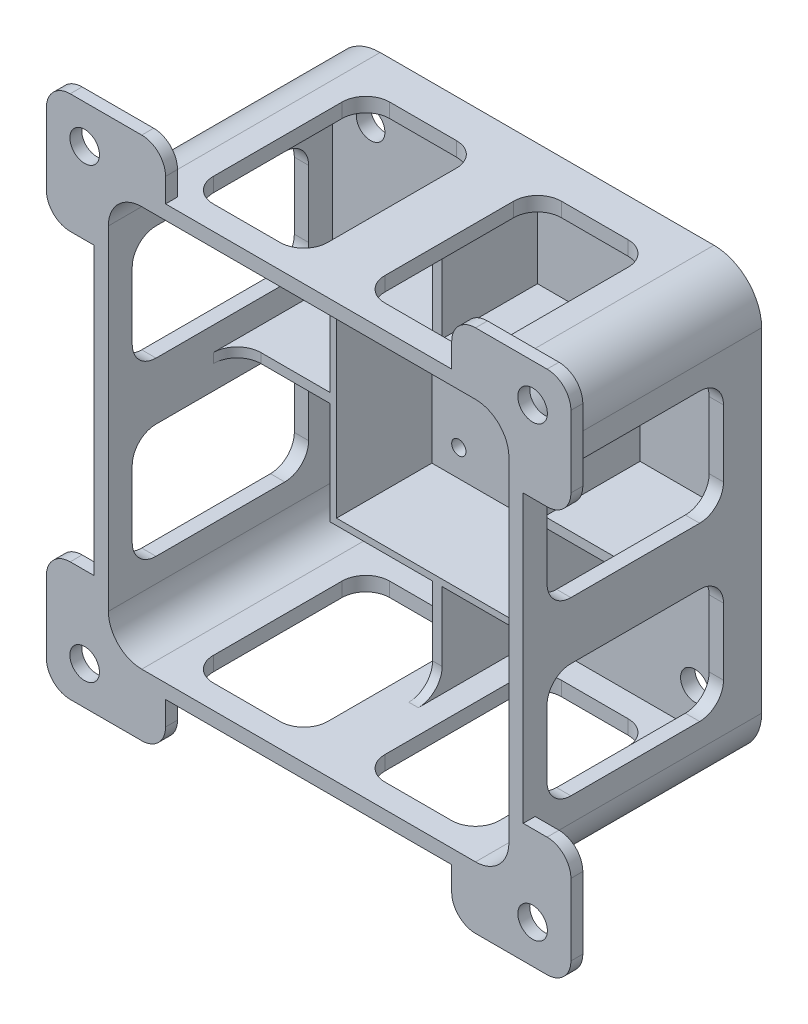
SolidWorks part; units mm, degrees
material "尼龙 101"
ref_plane "前视基准面" through (0, 0, 0) normal (0, 0, 1) x (1, 0, 0)
ref_plane "上视基准面" through (0, 0, 0) normal (0, 1, 0) x (1, 0, 0)
ref_plane "右视基准面" through (0, 0, 0) normal (1, 0, 0) x (0, 0, -1)
sketch "草图1" plane through (0, 0, 0) normal (0, 0, 1) x (1, 0, 0)
  line L1 (-35, 45) -> (35, 45)
  line L2 (-45, 35) -> (-45, -35)
  line L3 (-35, -45) -> (35, -45)
  line L4 (45, 35) -> (45, -35)
  line L5 (-45, 45) -> (45, -45) construction
  line L6 (-45, -45) -> (45, 45) construction
  arc A0 (-45, -35) -> (-35, -45) centre (-35, -35) ccw
  arc A1 (35, -45) -> (45, -35) centre (35, -35) ccw
  arc A2 (35, 45) -> (45, 35) centre (35, 35) cw
  arc A3 (-35, 45) -> (-45, 35) centre (-35, 35) ccw
  point P0 (0, 0)
  dimension "D3" = 10
  dimension "D1" = 90
  dimension "D2" = 90
extrude "凸台-拉伸1" add sketch "草图1" along normal blind 50
shell "抽壳1" thickness 3 removed face at (0, 0, 50)
sketch "草图3" plane through (0, 0, 50) normal (0, 0, 1) x (1, 0, 0)
  line L1 (0, 0) -> (0, 55.6478) construction
  line L2 (0, 0) -> (103.6974, 0) construction
  circle A0 centre (-34, 34) radius 3
  circle A1 centre (34, 34) radius 3
  circle A2 centre (34, -34) radius 3
  circle A3 centre (-34, -34) radius 3
  dimension "D3" = 6
  dimension "D4" = 6
  dimension "D5" = 6
  dimension "D6" = 6
  dimension "D1" = 68
  dimension "D2" = 68
extrude "切除-拉伸1" cut sketch "草图3" against normal up to next
sketch "草图4" plane through (0, 0, 3) normal (0, 0, 1) x (1, 0, 0)
  line L1 (-21.15, -21.15) -> (21.15, -21.15)
  line L2 (-21.15, -21.15) -> (-21.15, 21.15)
  line L3 (-21.15, 21.15) -> (21.15, 21.15)
  line L4 (21.15, -21.15) -> (21.15, 21.15)
  line L5 (-21.15, -21.15) -> (21.15, 21.15) construction
  line L6 (-21.15, 21.15) -> (21.15, -21.15) construction
  line L7 (-22.5, -22.5) -> (22.5, -22.5)
  line L8 (-22.5, -22.5) -> (-22.5, 22.5)
  line L9 (-22.5, 22.5) -> (22.5, 22.5)
  line L10 (22.5, -22.5) -> (22.5, 22.5)
  line L11 (-22.5, -22.5) -> (22.5, 22.5) construction
  line L12 (-22.5, 22.5) -> (22.5, -22.5) construction
  point P0 (0, 0)
  point P6 (0, 0)
  dimension "D1" = 42.3
  dimension "D2" = 42.3
  dimension "D3" = 45
  dimension "D4" = 45
extrude "凸台-拉伸3" add sketch "草图4" along normal blind 20
sketch "草图11" plane through (0, 0, 3) normal (0, 0, 1) x (1, 0, 0)
  line L0 (-15.5, -15.5) -> (-15.5, 15.5) construction
  line L1 (-15.5, 15.5) -> (15.5, 15.5) construction
  line L2 (15.5, 15.5) -> (15.5, -15.5) construction
  line L3 (15.5, -15.5) -> (-15.5, -15.5) construction
  line L4 (0, 0) -> (34.4126, 0) construction
  line L5 (0, 0) -> (0, 49.7231) construction
  circle A0 centre (-15.5, -15.5) radius 1.5
  circle A1 centre (15.5, -15.5) radius 1.5
  circle A2 centre (15.5, 15.5) radius 1.5
  circle A3 centre (-15.5, 15.5) radius 1.5
  dimension "D3" = 3
  dimension "D4" = 3
  dimension "D5" = 3
  dimension "D6" = 3
  dimension "D1" = 31
  dimension "D2" = 31
extrude "切除-拉伸4" cut sketch "草图11" against normal through all
sketch "草图7" plane through (0, 0, 3) normal (0, 0, 1) x (1, 0, 0)
  line L0 (22.5, 22.5) -> (-22.5, 22.5) construction
  line L1 (-1, 42) -> (1, 42)
  line L2 (-1, 42) -> (-1, 22.5)
  line L3 (-1, 22.5) -> (1, 22.5)
  line L4 (1, 42) -> (1, 22.5)
  line L5 (-1, 42) -> (1, 22.5) construction
  line L6 (-1, 22.5) -> (1, 42) construction
  line L7 (-35, -42) -> (35, -42) construction
  line L8 (-1, -22.5) -> (1, -22.5)
  line L9 (-1, -22.5) -> (-1, -42)
  line L10 (-1, -42) -> (1, -42)
  line L11 (1, -22.5) -> (1, -42)
  line L12 (-1, -22.5) -> (1, -42) construction
  line L13 (-1, -42) -> (1, -22.5) construction
  line L14 (0, 32.25) -> (0, 0) construction
  line L15 (0, 0) -> (0, -32.25) construction
  line L16 (35, 42) -> (-35, 42) construction
  line L17 (-22.5, -22.5) -> (22.5, -22.5) construction
  point P0 (0, 32.25)
  point P7 (0, -32.25)
  dimension "D1" = 2
  dimension "D2" = 2
extrude "凸台-拉伸5" add sketch "草图7" along normal up to surface (20 mm away) up to face at (0, 0, 23)
ref_axis "基准轴1" through (0, 0, -2) along (0, 0, 1)
pattern_circular "阵列(圆周)1" count 2 over 90 about axis through (0, 0, -2) along (0, 0, 1) of "凸台-拉伸5"
sketch "草图10" plane through (0, 0, 0) normal (0, 0, -1) x (-1, 0, 0)
  circle A0 centre (0, 0) radius 5
  dimension "D1" = 10
extrude "切除-拉伸3" cut sketch "草图10" against normal through all
fillet "圆角1" radius 5 4 edges at (-42, 0, 23) (42, 0, 23) (0, -42, 23) (0, 42, 23)
sketch "草图12" plane through (0, 0, 50) normal (0, 0, 1) x (1, 0, 0)
  line L5 (42, -30) -> (50, -30)
  line L6 (30, -42) -> (30, -50)
  line L7 (35, -55) -> (50, -55)
  line L8 (55, -35) -> (55, -50)
  line L19 (42, -35) -> (42, 35) construction
  line L20 (35, -42) -> (30, -42)
  line L21 (-35, -42) -> (35, -42) construction
  line L22 (42, -35) -> (42, -30)
  line L23 (0, 0) -> (0, -109.4281) construction
  line L24 (-42, -35) -> (-42, -30)
  line L25 (-35, -42) -> (-30, -42)
  line L27 (-55, -35) -> (-55, -50)
  line L28 (-35, -55) -> (-50, -55)
  line L29 (-30, -42) -> (-30, -50)
  line L30 (-42, -30) -> (-50, -30)
  line L36 (45, -35) -> (45, 35) construction
  line L37 (-35, -45) -> (35, -45) construction
  line L38 (0, 0) -> (81.8006, 0) construction
  line L39 (-42, 30) -> (-50, 30)
  line L40 (-30, 42) -> (-30, 50)
  line L41 (-35, 55) -> (-50, 55)
  line L42 (-55, 35) -> (-55, 50)
  line L43 (-35, 42) -> (-30, 42)
  line L44 (-42, 35) -> (-42, 30)
  line L45 (42, 35) -> (42, 30)
  line L46 (35, 42) -> (30, 42)
  line L47 (55, 35) -> (55, 50)
  line L48 (35, 55) -> (50, 55)
  line L49 (30, 42) -> (30, 50)
  line L50 (42, 30) -> (50, 30)
  arc A1 (-42, 35) -> (-35, 42) centre (-35, 35) cw
  arc A2 (-30, 50) -> (-35, 55) centre (-35, 50) ccw
  arc A3 (-50, 55) -> (-55, 50) centre (-50, 50) ccw
  arc A4 (42, -35) -> (35, -42) centre (35, -35) cw
  arc A5 (30, -50) -> (35, -55) centre (35, -50) ccw
  arc A6 (50, -55) -> (55, -50) centre (50, -50) ccw
  arc A7 (50, -30) -> (55, -35) centre (50, -35) cw
  arc A22 (-50, -30) -> (-55, -35) centre (-50, -35) ccw
  arc A23 (-50, -55) -> (-55, -50) centre (-50, -50) cw
  arc A24 (-30, -50) -> (-35, -55) centre (-35, -50) cw
  arc A25 (-42, -35) -> (-35, -42) centre (-35, -35) ccw
  arc A27 (-50, 30) -> (-55, 35) centre (-50, 35) cw
  arc A28 (50, 30) -> (55, 35) centre (50, 35) ccw
  arc A29 (50, 55) -> (55, 50) centre (50, 50) cw
  arc A30 (30, 50) -> (35, 55) centre (35, 50) cw
  arc A31 (42, 35) -> (35, 42) centre (35, 35) ccw
  dimension "D5" = 5
  dimension "D6" = 10
  dimension "D3" = 25
  dimension "D4" = 25
  dimension "D7" = 10
extrude "凸台-拉伸6" add sketch "草图12" against normal blind 2.5
sketch "草图13" plane through (0, 0, 47.5) normal (0, 0, -1) x (-1, 0, 0)
  line L0 (-55, -50) -> (-55, -35) construction
  line L1 (-35, -55) -> (-50, -55) construction
  line L2 (-55, 35) -> (-55, 50) construction
  line L3 (-50, 55) -> (-35, 55) construction
  line L4 (55, 50) -> (55, 35) construction
  line L5 (35, 55) -> (50, 55) construction
  line L6 (50, -55) -> (35, -55) construction
  line L7 (55, -35) -> (55, -50) construction
  circle A0 centre (-46.97, -46.97) radius 3.1
  circle A1 centre (-46.97, 46.97) radius 3.1
  circle A2 centre (46.97, 46.97) radius 3.1
  circle A3 centre (46.97, -46.97) radius 3.1
  dimension "D9" = 6.2
  dimension "D10" = 6.2
  dimension "D11" = 6.2
  dimension "D12" = 6.2
  dimension "D1" = 8.03
  dimension "D2" = 8.03
  dimension "D3" = 8.03
  dimension "D4" = 8.03
  dimension "D5" = 8.03
  dimension "D6" = 8.03
  dimension "D7" = 8.03
  dimension "D8" = 8.03
extrude "切除-拉伸5" cut sketch "草图13" against normal through all
sketch "草图14" plane through (0, 42, 0) normal (0, -1, 0) x (1, 0, 0)
  line L0 (35, 50) -> (35, 3) construction
  line L1 (25, 45) -> (11, 45)
  line L2 (30, 40) -> (30, 13)
  line L3 (25, 8) -> (11, 8)
  line L4 (6, 40) -> (6, 13)
  line L5 (35, 3) -> (1, 3) construction
  line L6 (1, 28) -> (1, 3) construction
  line L7 (35, 50) -> (-35, 50) construction
  line L8 (0, 0) -> (0, 105.1469) construction
  line L9 (-6, 40) -> (-6, 13)
  line L10 (-25, 8) -> (-11, 8)
  line L11 (-30, 40) -> (-30, 13)
  line L12 (-25, 45) -> (-11, 45)
  arc A0 (11, 45) -> (6, 40) centre (11, 40) ccw
  arc A1 (11, 8) -> (6, 13) centre (11, 13) cw
  arc A2 (30, 13) -> (25, 8) centre (25, 13) cw
  arc A3 (25, 45) -> (30, 40) centre (25, 40) cw
  arc A4 (-25, 45) -> (-30, 40) centre (-25, 40) ccw
  arc A5 (-30, 13) -> (-25, 8) centre (-25, 13) ccw
  arc A6 (-11, 8) -> (-6, 13) centre (-11, 13) ccw
  arc A7 (-11, 45) -> (-6, 40) centre (-11, 40) cw
  dimension "D5" = 5
  dimension "D1" = 5
  dimension "D2" = 5
  dimension "D3" = 5
  dimension "D4" = 5
extrude "切除-拉伸6" cut sketch "草图14" against normal through all
sketch "草图15" plane through (0, -42, 0) normal (0, 1, 0) x (1, 0, 0)
  line L0 (30, -13) -> (30, -40) construction
  line L1 (25, -45) -> (11, -45) construction
  line L2 (6, -40) -> (6, -13) construction
  line L3 (11, -8) -> (25, -8) construction
  line L4 (30, -13) -> (30, -40)
  line L5 (25, -45) -> (11, -45)
  line L6 (6, -40) -> (6, -13)
  line L7 (11, -8) -> (25, -8)
  line L8 (-6, -13) -> (-6, -40) construction
  line L9 (-11, -45) -> (-25, -45) construction
  line L10 (-30, -40) -> (-30, -13) construction
  line L11 (-25, -8) -> (-11, -8) construction
  line L12 (-25, -8) -> (-11, -8)
  line L13 (-30, -40) -> (-30, -13)
  line L14 (-6, -13) -> (-6, -40)
  line L15 (-11, -45) -> (-25, -45)
  arc A0 (25, -45) -> (30, -40) centre (25, -40) ccw construction
  arc A1 (6, -40) -> (11, -45) centre (11, -40) ccw construction
  arc A2 (11, -8) -> (6, -13) centre (11, -13) ccw construction
  arc A3 (30, -13) -> (25, -8) centre (25, -13) ccw construction
  arc A4 (25, -45) -> (30, -40) centre (25, -40) ccw
  arc A5 (6, -40) -> (11, -45) centre (11, -40) ccw
  arc A6 (11, -8) -> (6, -13) centre (11, -13) ccw
  arc A7 (30, -13) -> (25, -8) centre (25, -13) ccw
  arc A8 (-11, -45) -> (-6, -40) centre (-11, -40) ccw construction
  arc A9 (-30, -40) -> (-25, -45) centre (-25, -40) ccw construction
  arc A10 (-25, -8) -> (-30, -13) centre (-25, -13) ccw construction
  arc A11 (-6, -13) -> (-11, -8) centre (-11, -13) ccw construction
  arc A12 (-6, -13) -> (-11, -8) centre (-11, -13) ccw
  arc A13 (-25, -8) -> (-30, -13) centre (-25, -13) ccw
  arc A14 (-30, -40) -> (-25, -45) centre (-25, -40) ccw
  arc A15 (-11, -45) -> (-6, -40) centre (-11, -40) ccw
extrude "切除-拉伸7" cut sketch "草图15" against normal through all
pattern_circular "阵列(圆周)2" count 4 over 360 about axis through (0, 0, -2) along (0, 0, 1) of "切除-拉伸6"
